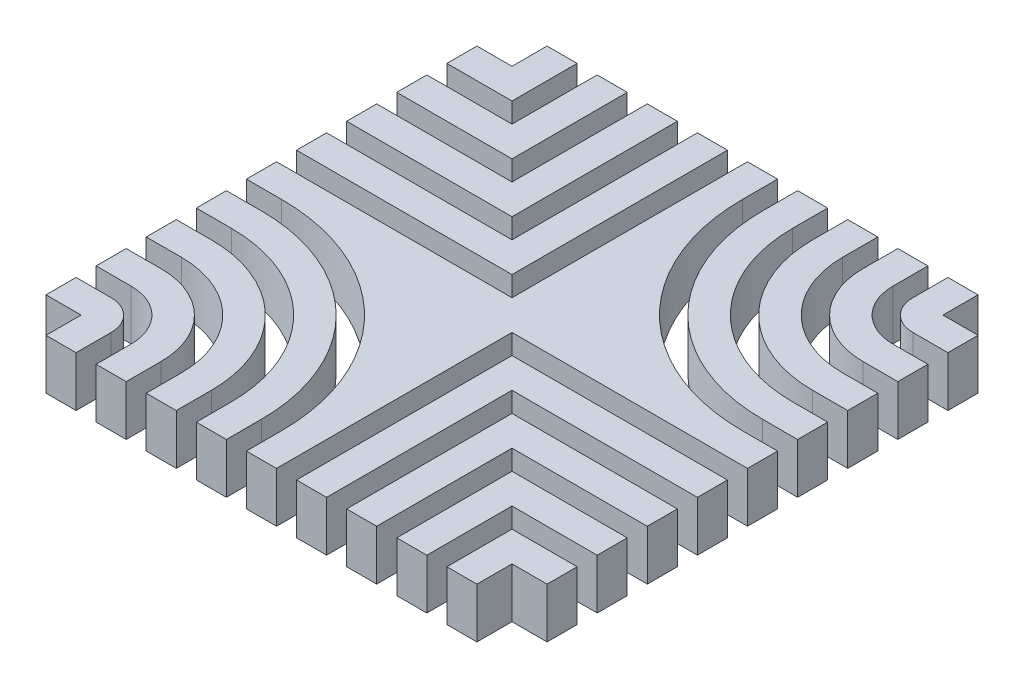
SolidWorks part; units mm, degrees
ref_plane "Front Plane" through (0, 0, 0) normal (0, 0, 1) x (1, 0, 0)
ref_plane "Top Plane" through (0, 0, 0) normal (0, 1, 0) x (1, 0, 0)
ref_plane "Right Plane" through (0, 0, 0) normal (1, 0, 0) x (0, 0, -1)
sketch "Sketch1" plane through (0, 0, 0) normal (0, 1, 0) x (1, 0, 0)
  line L0 (0, 50) -> (0, -50) construction
  line L1 (-50, 0) -> (50, 0) construction
  line L2 (-50, -10) -> (-10, -10) construction
  line L3 (-10, 50) -> (-10, 10) construction
  line L4 (-50, 10) -> (-10, 10) construction
  line L5 (10, 50) -> (10, 10) construction
  line L6 (10, 10) -> (50, 10) construction
  line L7 (-50, 10) -> (50, 10) construction
  line L8 (-10, -10) -> (-10, -50) construction
  line L9 (-10, 50) -> (-10, -50) construction
  line L10 (10, -10) -> (10, -50) construction
  line L11 (10, 50) -> (10, -50) construction
  line L12 (10, -10) -> (50, -10) construction
  line L13 (-50, -10) -> (50, -10) construction
  line L14 (-20, 50) -> (-20, 20) construction
  line L15 (-50, 20) -> (-20, 20) construction
  line L16 (20, 50) -> (20, 20) construction
  line L17 (20, 20) -> (50, 20) construction
  line L18 (20, -20) -> (20, -50) construction
  line L19 (20, -20) -> (50, -20) construction
  line L20 (-50, -20) -> (-20, -20) construction
  line L21 (-20, -20) -> (-20, -50) construction
  line L22 (-50, -30) -> (-30, -30) construction
  line L23 (-30, -30) -> (-30, -50) construction
  line L24 (30, -30) -> (30, -50) construction
  line L25 (30, -30) -> (50, -30) construction
  line L26 (30, 50) -> (30, 30) construction
  line L27 (30, 30) -> (50, 30) construction
  line L28 (-50, 30) -> (-30, 30) construction
  line L29 (-30, 50) -> (-30, 30) construction
  line L30 (-50, -40) -> (-40, -40) construction
  line L31 (-40, -40) -> (-40, -50) construction
  line L32 (40, -40) -> (40, -50) construction
  line L33 (40, -40) -> (50, -40) construction
  line L34 (-50, 40) -> (-40, 40) construction
  line L35 (-40, 50) -> (-40, 40) construction
  line L36 (40, 50) -> (40, 40) construction
  line L37 (40, 40) -> (50, 40) construction
  line L38 (-50, 37) -> (-37, 37)
  line L39 (-37, 50) -> (-37, 37)
  line L40 (-50, 27) -> (-27, 27)
  line L41 (-27, 50) -> (-27, 27)
  line L42 (-50, 17) -> (-17, 17)
  line L43 (-17, 50) -> (-17, 17)
  line L44 (-50, 7) -> (-7, 7)
  line L45 (-7, 50) -> (-7, 7)
  line L46 (-50, -3) -> (-43, -3)
  line L47 (-50, 43) -> (-43, 43)
  line L48 (-43, 50) -> (-43, 43)
  line L49 (-50, 33) -> (-33, 33)
  line L50 (-33, 50) -> (-33, 33)
  line L51 (-50, 23) -> (-23, 23)
  line L52 (-23, 50) -> (-23, 23)
  line L53 (-50, 13) -> (-13, 13)
  line L54 (-13, 50) -> (-13, 13)
  line L55 (-50, 3) -> (-3, 3)
  line L56 (-50, -13) -> (-43, -13)
  line L57 (-13, -43) -> (-13, -50)
  line L58 (-50, -23) -> (-43, -23)
  line L59 (-23, -43) -> (-23, -50)
  line L60 (-50, -33) -> (-43, -33)
  line L61 (-33, -43) -> (-33, -50)
  line L62 (-50, -43) -> (-43, -43)
  line L63 (-43, -43) -> (-43, -50)
  line L64 (7, -7) -> (50, -7)
  line L65 (7, -7) -> (7, -50)
  line L66 (17, -17) -> (50, -17)
  line L67 (17, -17) -> (17, -50)
  line L68 (27, -27) -> (50, -27)
  line L69 (27, -27) -> (27, -50)
  line L70 (37, -37) -> (50, -37)
  line L71 (37, -37) -> (37, -50)
  line L72 (7, 50) -> (7, 43)
  line L73 (43, 7) -> (50, 7)
  line L74 (-50, -7) -> (-43, -7)
  line L75 (-7, -43) -> (-7, -50)
  line L76 (-50, -17) -> (-43, -17)
  line L77 (-17, -43) -> (-17, -50)
  line L78 (-50, -27) -> (-43, -27)
  line L79 (-27, -43) -> (-27, -50)
  line L80 (-50, -37) -> (-43, -37)
  line L81 (-37, -43) -> (-37, -50)
  line L82 (13, -13) -> (50, -13)
  line L83 (13, -13) -> (13, -50)
  line L84 (23, -23) -> (50, -23)
  line L85 (23, -23) -> (23, -50)
  line L86 (33, -33) -> (50, -33)
  line L87 (33, -33) -> (33, -50)
  line L88 (43, -43) -> (50, -43)
  line L89 (43, -43) -> (43, -50)
  line L90 (13, 50) -> (13, 43)
  line L91 (43, 13) -> (50, 13)
  line L92 (17, 50) -> (17, 43)
  line L93 (43, 17) -> (50, 17)
  line L94 (23, 50) -> (23, 43)
  line L95 (43, 23) -> (50, 23)
  line L96 (27, 50) -> (27, 43)
  line L97 (43, 27) -> (50, 27)
  line L98 (37, 50) -> (37, 43)
  line L99 (43, 37) -> (50, 37)
  line L100 (33, 50) -> (33, 43)
  line L101 (43, 33) -> (50, 33)
  line L102 (43, 50) -> (43, 43)
  line L103 (43, 43) -> (50, 43)
  line L104 (-3, 50) -> (-3, 3)
  line L105 (3, 50) -> (3, 43)
  line L106 (-33, -50) -> (-27, -50)
  line L107 (-43, 50) -> (-37, 50)
  line L108 (-50, 43) -> (-50, 37)
  line L109 (-43, -50) -> (-37, -50)
  line L110 (50, 43) -> (50, 37)
  line L111 (-50, -7) -> (-7, -7) construction
  line L112 (-7, -7) -> (-7, -50) construction
  line L113 (-23, -50) -> (-17, -50)
  line L114 (-13, -50) -> (-7, -50)
  line L115 (-3, -50) -> (3, -50)
  line L116 (7, -50) -> (13, -50)
  line L117 (17, -50) -> (23, -50)
  line L118 (27, -50) -> (33, -50)
  line L119 (37, -50) -> (43, -50)
  line L120 (50, -37) -> (50, -43)
  line L121 (50, -27) -> (50, -33)
  line L122 (50, -17) -> (50, -23)
  line L123 (50, -7) -> (50, -13)
  line L124 (50, 3) -> (50, -3)
  line L125 (50, 13) -> (50, 7)
  line L126 (50, 23) -> (50, 17)
  line L127 (50, 33) -> (50, 27)
  line L128 (37, 50) -> (43, 50)
  line L129 (27, 50) -> (33, 50)
  line L130 (17, 50) -> (23, 50)
  line L131 (7, 50) -> (13, 50)
  line L132 (-3, 50) -> (3, 50)
  line L133 (-13, 50) -> (-7, 50)
  line L134 (-23, 50) -> (-17, 50)
  line L135 (-33, 50) -> (-27, 50)
  line L136 (-50, 33) -> (-50, 27)
  line L137 (-50, 23) -> (-50, 17)
  line L138 (-50, 13) -> (-50, 7)
  line L139 (-50, 3) -> (-50, -3)
  line L140 (-50, -7) -> (-50, -13)
  line L141 (-50, -17) -> (-50, -23)
  line L142 (-50, -27) -> (-50, -33)
  line L143 (-50, -37) -> (-50, -43)
  line L144 (43, 3) -> (50, 3)
  line L145 (-50, 3) -> (50, 3) construction
  line L146 (-3, -43) -> (-3, -50)
  line L147 (-3, 50) -> (-3, -50) construction
  line L148 (3, -3) -> (3, -50)
  line L149 (3, 50) -> (3, -50) construction
  line L150 (3, -3) -> (50, -3)
  line L151 (-50, -3) -> (50, -3) construction
  line L152 (-50, -13) -> (-13, -13) construction
  line L153 (-13, -13) -> (-13, -50) construction
  line L154 (-50, -17) -> (-17, -17) construction
  line L155 (-17, -17) -> (-17, -50) construction
  line L156 (-50, -23) -> (-23, -23) construction
  line L157 (-23, -23) -> (-23, -50) construction
  line L158 (-50, -27) -> (-27, -27) construction
  line L159 (-27, -27) -> (-27, -50) construction
  line L160 (-50, -33) -> (-33, -33) construction
  line L161 (-33, -33) -> (-33, -50) construction
  line L162 (-50, -37) -> (-37, -37) construction
  line L163 (-37, -37) -> (-37, -50) construction
  line L164 (37, 50) -> (37, 37) construction
  line L165 (37, 37) -> (50, 37) construction
  line L166 (33, 50) -> (33, 33) construction
  line L167 (33, 33) -> (50, 33) construction
  line L168 (27, 50) -> (27, 27) construction
  line L169 (27, 27) -> (50, 27) construction
  line L170 (23, 50) -> (23, 23) construction
  line L171 (23, 23) -> (50, 23) construction
  line L172 (17, 50) -> (17, 17) construction
  line L173 (17, 17) -> (50, 17) construction
  line L174 (13, 50) -> (13, 13) construction
  line L175 (13, 13) -> (50, 13) construction
  line L176 (7, 50) -> (7, 7) construction
  line L177 (7, 7) -> (50, 7) construction
  arc A0 (-43, -7) -> (-7, -43) centre (-43, -43) cw
  arc A1 (-43, -13) -> (-13, -43) centre (-43, -43) cw
  arc A2 (-43, -17) -> (-17, -43) centre (-43, -43) cw
  arc A3 (-43, -23) -> (-23, -43) centre (-43, -43) cw
  arc A4 (-43, -27) -> (-27, -43) centre (-43, -43) cw
  arc A5 (-43, -33) -> (-33, -43) centre (-43, -43) cw
  arc A6 (-43, -37) -> (-37, -43) centre (-43, -43) cw
  arc A7 (37, 43) -> (43, 37) centre (43, 43) ccw
  arc A8 (33, 43) -> (43, 33) centre (43, 43) ccw
  arc A9 (27, 43) -> (43, 27) centre (43, 43) ccw
  arc A10 (23, 43) -> (43, 23) centre (43, 43) ccw
  arc A11 (17, 43) -> (43, 17) centre (43, 43) ccw
  arc A12 (13, 43) -> (43, 13) centre (43, 43) ccw
  arc A13 (7, 43) -> (43, 7) centre (43, 43) ccw
  arc A14 (43, 3) -> (3, 43) centre (43, 43) cw
  arc A15 (-3, -43) -> (-43, -3) centre (-43, -43) ccw
  point P4 (0, 0)
  point P8 (0, 0)
  point P160 (0, 0)
  point P163 (0, 0)
  point P164 (0, 0)
  point P165 (0, 0)
  point P188 (0, 0)
  point P189 (0, 0)
  dimension "D21" = 6
  dimension "D22" = 10
  dimension "D23" = 16
  dimension "D24" = 20
  dimension "D25" = 26
  dimension "D26" = 30
  dimension "D27" = 36
  dimension "D28" = 6
  dimension "D29" = 10
  dimension "D30" = 16
  dimension "D31" = 20
  dimension "D32" = 26
  dimension "D33" = 30
  dimension "D34" = 36
  dimension "D35" = 40
  dimension "D36" = 40
  dimension "D1" = 100
  dimension "D2" = 100
  dimension "D3" = 10
  dimension "D4" = 10
  dimension "D5" = 10
  dimension "D6" = 10
  dimension "D7" = 10
  dimension "D8" = 10
  dimension "D9" = 10
  dimension "D10" = 10
  dimension "D11" = 3
  dimension "D12" = 3
  dimension "D13" = 3
  dimension "D14" = 3
  dimension "D15" = 3
  dimension "D16" = 3
  dimension "D17" = 3
  dimension "D18" = 3
  dimension "D19" = 3
  dimension "D20" = 3
extrude "Boss-Extrude1" add sketch "Sketch1" along normal blind 10
